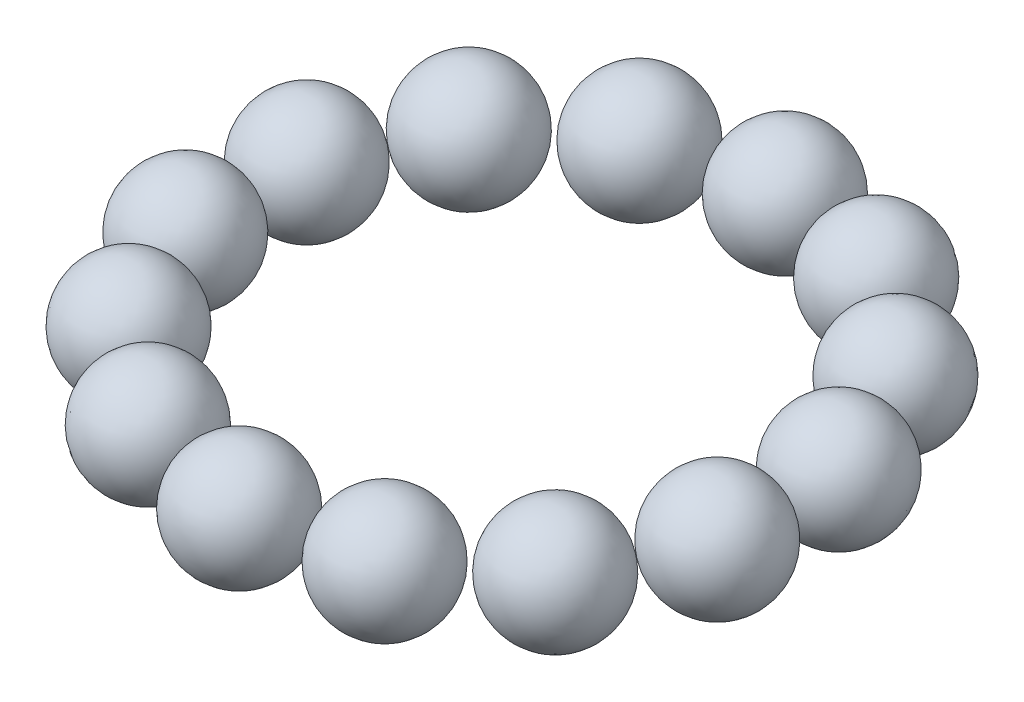
SolidWorks part; units mm, degrees
material "Chrome Stainless Steel"
ref_plane "Front Plane" through (0, 0, 0) normal (1, 0, 0) x (0, 1, 0)
ref_plane "Top Plane" through (0, 0, 0) normal (0, 0, 1) x (0, 1, 0)
ref_plane "Right Plane" through (0, 0, 0) normal (0, 1, 0) x (-1, 0, 0)
sketch "Sketch2" plane through (0, 0, 0) normal (1, 0, 0) x (0, 1, 0)
  line L0 (-31.8153, 0) -> (28.7982, 0) construction
  line L1 (0, 17) -> (0, -22.0859) construction
  line L2 (-3, 14) -> (3, 14)
  arc A0 (-3, 14) -> (3, 14) centre (0, 14) cw
  circle A1 centre (0, 0) radius 10
  point P8 (0, 14)
  point P10 (0, 17)
  dimension "D2" = 3
  dimension "D4" = 20
  dimension "D1" = 14
  dimension "D3" = 6
revolve "Revolve1" add sketch "Sketch2" angle 360 about L2 region at (0, 0, 15.2732)
pattern_circular "CirPattern2" count 14 over 360 about axis through (0, -31.8153, 0) along (0, 1, 0) of bodies 101
ref_axis "Axis1" through (0, 31.8289, 0) along (0, -1, 0)
